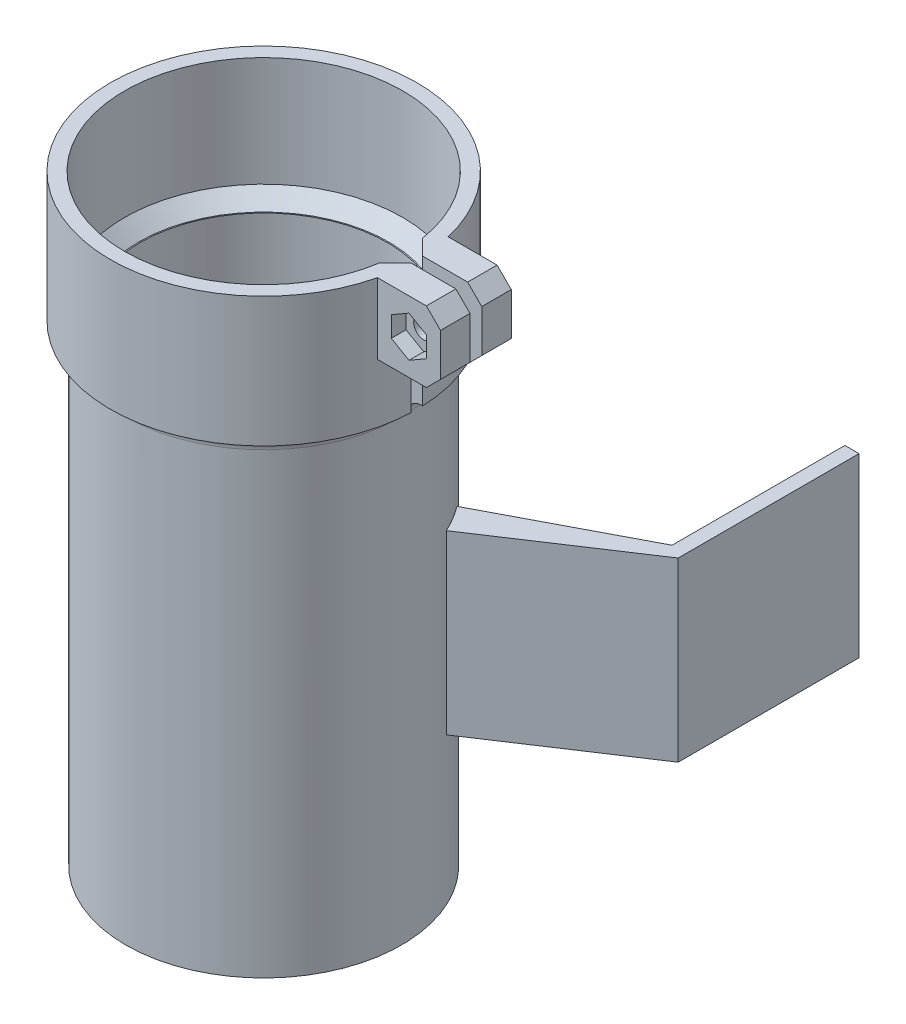
SolidWorks part; units mm, degrees
ref_plane "Front Plane" through (0, 0, 0) normal (0, 0, 1) x (1, 0, 0)
ref_plane "Top Plane" through (0, 0, 0) normal (0, 1, 0) x (1, 0, 0)
ref_plane "Right Plane" through (0, 0, 0) normal (1, 0, 0) x (0, 0, -1)
ref_plane "Plane2" through (24, 0, 0) normal (1, 0, 0) x (0, 0, -1)
sketch "AXIS OF CIRC PATTERN" plane through (0, 0, 0) normal (1, 0, 0) x (0, 0, -1)
  line L0 (0, 0) -> (0, 11.1323) construction
sketch "Sketch1" plane through (0, 0, 0) normal (0, 1, 0) x (1, 0, 0)
  circle A0 centre (0, 0) radius 21
  circle A1 centre (0, 0) radius 23.4
  dimension "D1" = 42
  dimension "D2" = 2.4
extrude "Boss-Extrude1" add sketch "Sketch1" along normal mid plane 80
sketch "Sketch7" plane through (0, 0, 0) normal (0, 1, 0) x (1, 0, 0)
  line L0 (43.8, 21) -> (43.8, 41) construction
  line L1 (43.8, 26) -> (0, 0) construction
  line L2 (0, 21) -> (43.8, 21) construction
  line L3 (45, 56) -> (42.6, 56)
  line L4 (45, 56) -> (45, 26)
  line L5 (18.6411, 14.1446) -> (18.9258, 11.2345)
  line L6 (45, 25.3168) -> (21.3085, 9.67)
  line L7 (42.6, 56) -> (42.6, 26.6832)
  line L8 (45, 56) -> (42.6, 26) construction
  line L9 (45, 26) -> (42.6, 56) construction
  line L10 (18.9258, 11.2345) -> (21.3085, 9.67)
  line L11 (45, 26) -> (45, 25.3168)
  line L13 (42.6, 26.6832) -> (18.6411, 14.1446)
  circle A0 centre (0, 0) radius 21 construction
  circle A1 centre (0, 0) radius 23.4 construction
  point P10 (43.1875, 27.0319)
  point P13 (-0.6125, 1.0319)
  point P14 (-0.613, 1.0316)
  point P15 (43.187, 27.0598)
  point P16 (44.4125, 24.9681)
  point P17 (0.6125, -1.0319)
  dimension "D1" = 43.8
  dimension "D2" = 20
  dimension "D3" = 2.4
  dimension "D4" = 30
extrude "Boss-Extrude5" add sketch "Sketch7" along normal mid plane 30
sketch "Sketch10" plane through (0, 0, 0) normal (0, 0, 1) x (1, 0, 0)
  line L1 (-7.5, 20) -> (7.5, 20)
  line L2 (-7.5, 20) -> (-7.5, -20)
  line L3 (-7.5, -20) -> (7.5, -20)
  line L4 (7.5, 20) -> (7.5, -20)
  line L5 (-7.5, 20) -> (7.5, -20) construction
  line L6 (-7.5, -20) -> (7.5, 20) construction
  point P0 (0, 0)
  dimension "D1" = 15
  dimension "D2" = 40
extrude "Cut-Extrude2" cut sketch "Sketch10" against normal blind 30
sketch "Sketch12" plane through (0, 40, 0) normal (0, 1, 0) x (1, 0, 0)
  circle A0 centre (0, 0) radius 23.6
  circle A1 centre (0, 0) radius 26
  dimension "D1" = 47.2
  dimension "D2" = 52
extrude "Boss-Extrude7" add sketch "Sketch12" along normal blind 22 separate body
sketch "Sketch13" plane through (0, 40, 0) normal (0, 1, 0) x (1, 0, 0)
  circle A0 centre (0, 0) radius 21
  circle A1 centre (0, 0) radius 26
  dimension "D1" = 42
extrude "Boss-Extrude8" add sketch "Sketch13" along normal blind 1
fillet "Fillet2" radius 2.4 1 edges at (0, 40, 23.4)
chamfer "Chamfer4" distance 2.4 angle 45 1 edges at (0, 41, 23.6)
sketch "Sketch14" plane through (24, 0, 0) normal (1, 0, 0) x (0, 0, -1)
  line L0 (0, 62) -> (0, 32.2869) construction
  line L1 (23.6, 62) -> (-23.6, 62) construction
  line L2 (0, 0) -> (0, 11.1323) construction
  line L4 (-6, 62) -> (6, 62)
  line L5 (-6, 62) -> (-6, 50)
  line L6 (-6, 50) -> (6, 50)
  line L7 (6, 62) -> (6, 50)
  line L8 (-6, 62) -> (6, 50) construction
  line L9 (-6, 50) -> (6, 62) construction
  point P6 (0, 56)
  dimension "D1" = 12
  dimension "D2" = 12
  dimension "D3" = 0
extrude "Boss-Extrude9" add sketch "Sketch14" along normal blind 12
sketch "Sketch15" plane through (0, 0, 0) normal (1, 0, 0) x (0, 0, -1)
  line L0 (0, 62) -> (0, 37.6) construction
  line L2 (6, 62) -> (-6, 62) construction
  line L3 (-23.4, 37.6) -> (23.4, 37.6) construction
  line L5 (-1, 62) -> (1, 62)
  line L6 (-1, 62) -> (-1, 37.6)
  line L7 (-1, 37.6) -> (1, 37.6)
  line L8 (1, 62) -> (1, 37.6)
  line L9 (-1, 62) -> (1, 37.6) construction
  line L10 (-1, 37.6) -> (1, 62) construction
  point P7 (0, 49.8)
  dimension "D1" = 2
extrude "Cut-Extrude3" cut sketch "Sketch15" along normal through all
sketch "Sketch16" plane through (0, 0, -6) normal (0, 0, -1) x (-1, 0, 0)
  line L0 (-36, 62) -> (-25.2982, 50) construction
  circle A0 centre (-30.6491, 56) radius 1.7
  dimension "D1" = 3.4
extrude "Cut-Extrude4" cut sketch "Sketch16" against normal through all
sketch "Sketch17" plane through (0, 0, -6) normal (0, 0, -1) x (-1, 0, 0)
  circle A0 centre (-30.6491, 56) radius 3
  dimension "D1" = 6
extrude "Cut-Extrude5" cut sketch "Sketch17" against normal blind 2.5
sketch "Sketch18" plane through (0, 0, 6) normal (0, 0, 1) x (1, 0, 0)
  line L1 (30.6491, 52.5359) -> (33.6491, 54.2679)
  line L2 (33.6491, 54.2679) -> (33.6491, 57.7321)
  line L3 (33.6491, 57.7321) -> (30.6491, 59.4641)
  line L4 (30.6491, 59.4641) -> (27.6491, 57.7321)
  line L5 (27.6491, 57.7321) -> (27.6491, 54.2679)
  line L6 (27.6491, 54.2679) -> (30.6491, 52.5359)
  circle A0 centre (30.6491, 56) radius 3 construction
  dimension "D1" = 6
extrude "Cut-Extrude6" cut sketch "Sketch18" against normal blind 2.5
chamfer "Chamfer5" distance 2.4 angle 45 6 edges at (23.5788, 52.7, 1) (23.5788, 52.7, -1) (36, 62, -3.5) (36, 50, -3.5) (36, 50, 3.5) (36, 62, 3.5) first distance on face at (30.6491, 57.7, 1) first distance on face at (30.6491, 54.3, -1) first distance on face at (17.9096, 62, 0) first distance on face at (30.8501, 50, -3.5041) first distance on face at (30.8501, 50, 3.5041)
